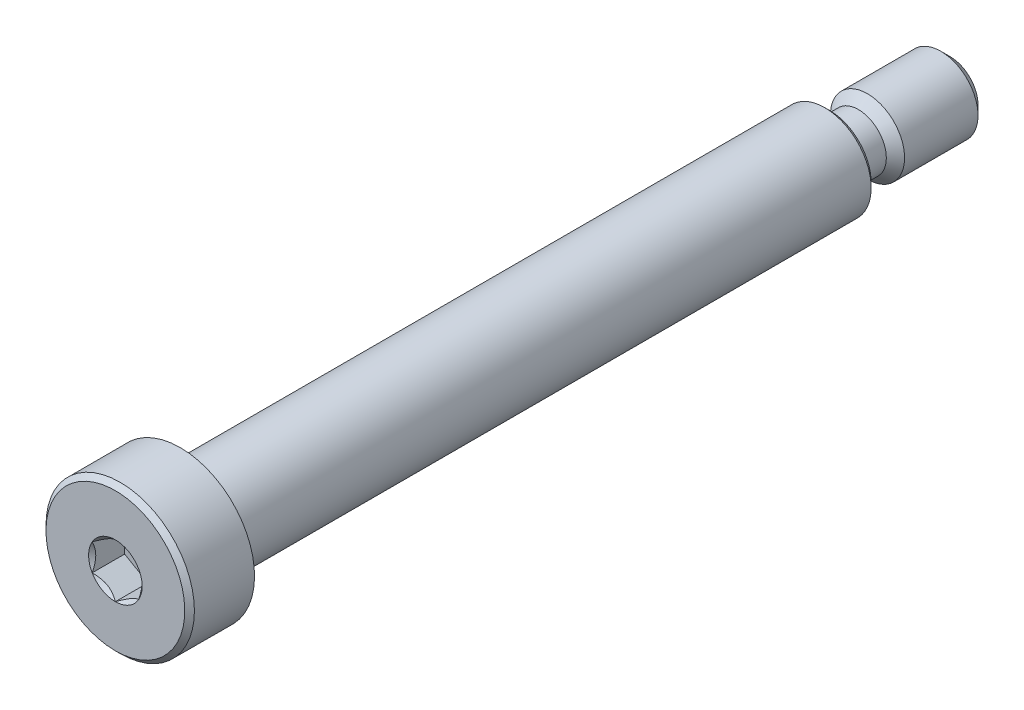
SolidWorks part; units mm, degrees
other "DetailItem1"
other "DetailItem2"
other "DetailItem5"
other "DetailItem6"
material "Steel AISI 4130 , normalized at 870°C"
ref_plane "Front" through (0, 0, 0) normal (0, 0, 1) x (1, 0, 0)
ref_plane "Top" through (0, 0, 0) normal (0, 1, 0) x (1, 0, 0)
ref_plane "Right" through (0, 0, 0) normal (1, 0, 0) x (0, 0, -1)
sketch "Sketch1" plane through (0, 0, 0) normal (1, 0, 0) x (0, 0, -1)
  line L0 (0, 8) -> (7, 8)
  line L1 (7, 8) -> (7, 5)
  line L2 (7, 5) -> (77, 5)
  line L3 (77, 5) -> (77, 4)
  line L4 (77, 4) -> (90, 4)
  line L5 (90, 4) -> (90, 0)
  line L6 (90, 0) -> (0, 0)
  line L7 (0, 0) -> (0, 8)
  line L8 (0, 8) -> (0, -8) construction
  line L9 (90, 4) -> (90, -4) construction
  line L10 (77, 5) -> (77, -5) construction
  point P8 (85.625, -4)
  point P12 (77, 0)
  dimension "Shoulder Dia" = 10
  dimension "Shoulder Lg" = 70
  dimension "D1" = 4.375
revolve "Revolve1" add sketch "Sketch1" angle 360 mid plane about L6
ref_plane "Plane1" through (0, 0, -90) normal (0, 0, 1) x (1, 0, 0)
sketch "Sketch3" plane through (0, 0, -90) normal (0, 0, 1) x (1, 0, 0)
  circle A0 centre (0, 0) radius 4
curve "Helix/Spiral1" pitch 1.25 height 14.25 turns 11.4
sketch "Sketch5" plane through (0, 0, 0) normal (1, 0, 0) x (0, 0, -1)
  line L0 (77, 5) -> (82.085, 5)
  line L1 (82.085, 5) -> (80.1, 3.015)
  line L2 (80.1, 3.015) -> (77.985, 3.015)
  line L3 (77, 5) -> (77, 4)
  line L5 (77, 4) -> (90, 4) construction
  line L6 (90, 0) -> (80.1, 0) construction
  line L7 (85.05, 0) -> (85.05, -4) construction
  arc A0 (77, 4) -> (77.985, 3.015) centre (77.985, 4) ccw
  dimension "D1" = 45
  dimension "CADB" = 3.1
  dimension "CADA" = 6.03
revolve "Cut-Revolve1" cut sketch "Sketch5" angle 360 mid plane about L6
chamfer "Chamfer1" distance 1 angle 45 1 edges at (0, 4, -90)
chamfer "Chamfer2" distance 0.52 angle 45 2 edges at (0, 8, 0) (0, 5, -77)
sketch "Sketch10" plane through (0, 0, 0) normal (1, 0, 0) x (0, 0, -1)
  line L0 (0.52, 0) -> (6.48, 0) construction
  line L1 (0.52, -8) -> (0.52, 8) construction
  line L3 (0.52, 0) -> (0, 0) construction
  line L4 (6.48, 0) -> (7, 0) construction
  line L5 (7, -8) -> (7, 8) construction
  point P6 (3.5, 0)
  dimension "D1" = 5.96
ref_plane "Plane2" through (0, 0, -3.5) normal (0, 0, 1) x (1, 0, 0)
sketch "Sketch11" plane through (0, 0, -3.5) normal (0, 0, 1) x (1, 0, 0)
  line L0 (0, 7.584) -> (0, 8) construction
  line L1 (0, 7.584) -> (0.2402, 8)
  line L2 (0, 7.584) -> (-0.2402, 8)
  line L3 (-0.2402, 8) -> (0.2402, 8)
  line L4 (0, 0) -> (-0.2402, 8) construction
  line L5 (0.2402, 8) -> (0, 0) construction
  circle A1 centre (0, 0) radius 8 construction
  circle A2 centre (0, 0) radius 7.584 construction
  circle A3 centre (0, 0) radius 7.48 construction
  point P3 (0, 0.0018)
  point P8 (2.3908, 0.7309)
  dimension "D1" = 0.416
  dimension "D2" = 3.439
extrude "Cut-Extrude5" [suppressed] cut sketch "Sketch11" against normal mid plane 5.662
pattern_circular "CirPattern1" [suppressed] count 99 over 360 of bodies 119
sketch "Sketch8" plane through (0, 0, 0) normal (0, 0, 1) x (1, 0, 0)
  line L1 (2.5, 1.4434) -> (0, 2.8868)
  line L2 (0, 2.8868) -> (-2.5, 1.4434)
  line L3 (-2.5, 1.4434) -> (-2.5, -1.4434)
  line L4 (-2.5, -1.4434) -> (0, -2.8868)
  line L5 (0, -2.8868) -> (2.5, -1.4434)
  line L6 (2.5, -1.4434) -> (2.5, 1.4434)
  circle A0 centre (0, 0) radius 2.5 construction
  dimension "Hex" = 5
extrude "Cut-Extrude2" cut sketch "Sketch8" against normal blind 3.5
sketch "Sketch9" plane through (0, 0, 0) normal (0, 0, 1) x (1, 0, 0)
  circle A0 centre (0, 0) radius 2.8868
extrude "Cut-Extrude4" cut sketch "Sketch9" against normal blind 3.5 draft 45
sketch "Sketch4" [suppressed] plane through (0, 0, 0) normal (1, 0, 0) x (0, 0, -1)
  line L0 (90, 4) -> (91.0938, 4)
  line L1 (91.0938, 4) -> (90.625, 3.1881)
  line L2 (90.625, 3.1881) -> (90.4688, 3.1881)
  line L3 (90.4688, 3.1881) -> (90, 4)
  line L4 (90.2344, 3.5941) -> (90.8594, 3.5941) construction
  dimension "D1" = 0.1562
  dimension "D2" = 0.625
  dimension "D3" = 60
sweep "Sweep1" [suppressed] add profiles "Sketch4" path "Helix/Spiral1"
sketch "Sketch6" [suppressed] plane through (0, 0, -77) normal (0, 0, -1) x (-1, 0, 0)
  circle A1 centre (0, 0) radius 4.48
  circle A2 centre (0, 0) radius 4.48
  dimension "D1" = 0
extrude "Cut-Extrude1" [suppressed] cut sketch "Sketch6" against normal through all from vertex
combine bodies "Combine1" [suppressed] operation type subtract main body 118 bodies to subtract 110
sketch "reference 1" plane through (0, 0, -7) normal (0, 0, -1) x (-1, 0, 0)
  circle A1 centre (0, 0) radius 8
  circle A2 centre (0, 0) radius 8 construction
equation "\"D3@Helix/Spiral1\" = \"Thread Lg@Sketch1\" + \"D4@Helix/Spiral1\""
equation "\"D1@Sketch4\" = \"D4@Helix/Spiral1\" * .125"
equation "\"D2@Sketch4\" = \"D4@Helix/Spiral1\" * .5"
equation "\"D1@Chamfer1\" = \"Thread Dia@Sketch1\" * .125"
equation "\"D1@Cut-Extrude2\"= \"Head Ht@Sketch1\" * .5"
equation "\"D1@Cut-Extrude4\" = \"D1@Cut-Extrude2\""
equation "\"D1@Chamfer2\" = \"Head Dia@Sketch1\" * .0325"
equation "\"D1@Sketch1\"=\"D4@Helix/Spiral1\"*3.5"
equation "\"D1@Sketch11\"=\"D1@Chamfer2\"*.8"
equation "\"D1@Cut-Extrude5\"=\"D1@Sketch10\"*.95"
equation "\"D1@CirPattern1\"=(360/\"D2@Sketch11\")-6"
